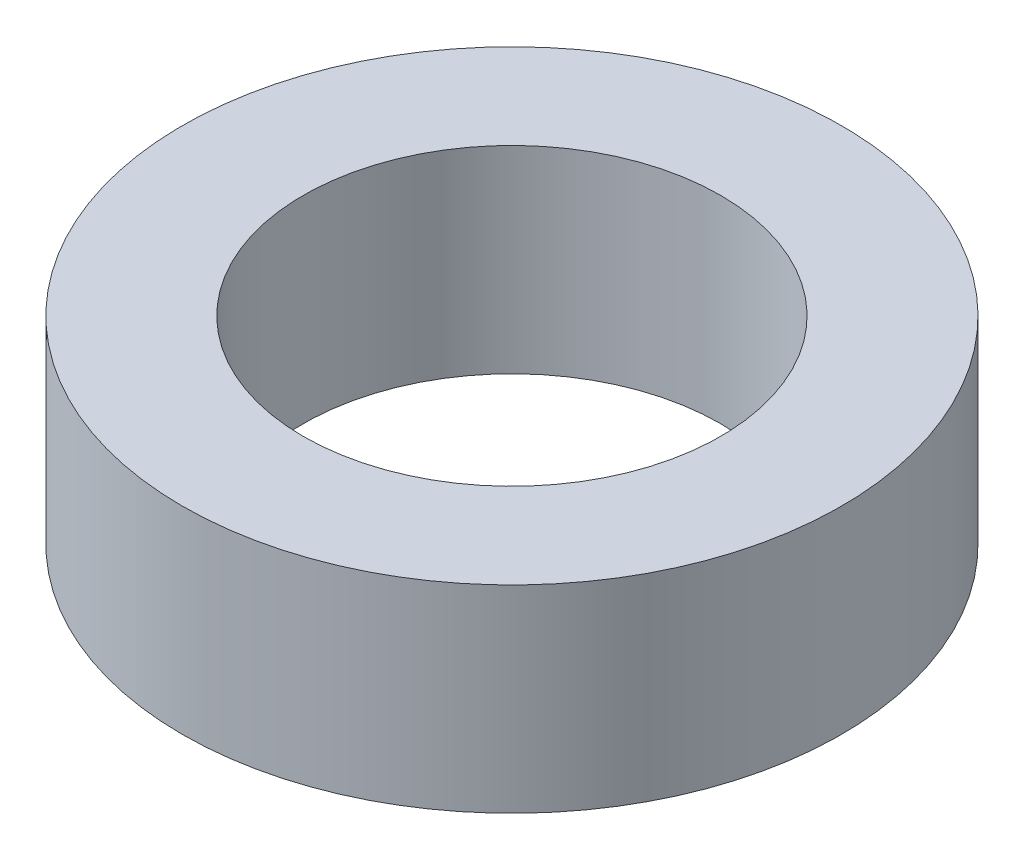
SolidWorks part; units mm, degrees
ref_plane "Front Plane" through (0, 0, 0) normal (0, 0, 1) x (1, 0, 0)
ref_plane "Top Plane" through (0, 0, 0) normal (0, 1, 0) x (1, 0, 0)
ref_plane "Right Plane" through (0, 0, 0) normal (1, 0, 0) x (0, 0, -1)
sketch "Sketch1" plane through (0, 0, 0) normal (0, 1, 0) x (1, 0, 0)
  circle A0 centre (0, 0) radius 15
extrude "Boss-Extrude1" add sketch "Sketch1" along normal blind 9
sketch "Sketch5" plane through (0, 9, 0) normal (0, 1, 0) x (1, 0, 0)
  circle A0 centre (0, 0) radius 9.5
extrude "Cut-Extrude3" cut sketch "Sketch5" against normal through all
move or copy body "Body-Move/Copy1" [suppressed] bodies to move or copy 106
